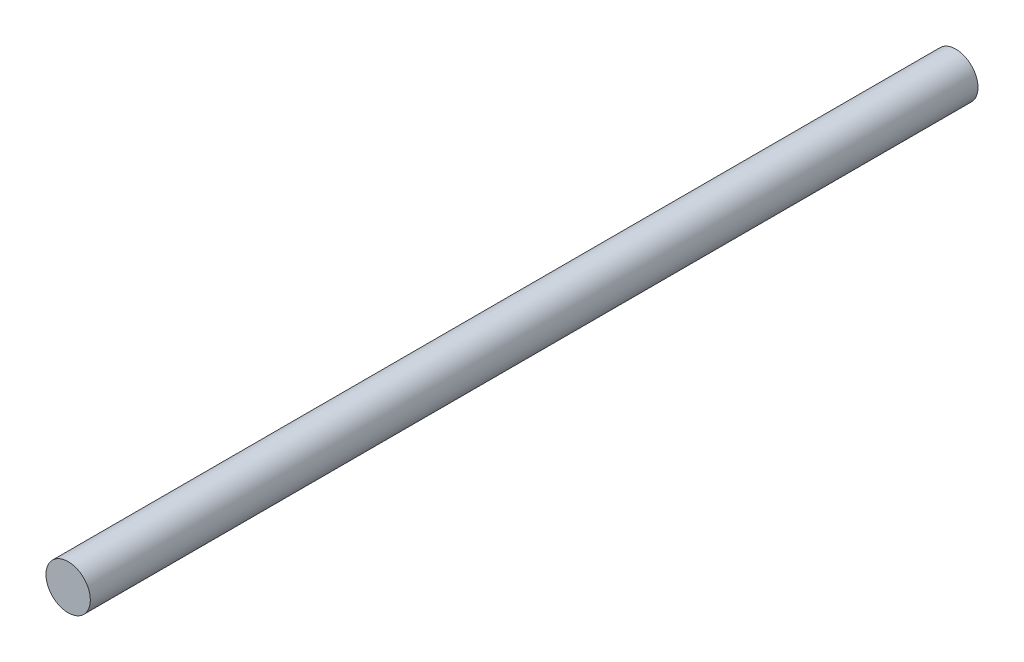
SolidWorks part; units mm, degrees
ref_plane "Front" through (0, 0, 0) normal (0, 0, 1) x (1, 0, 0)
ref_plane "Top" through (0, 0, 0) normal (0, 1, 0) x (1, 0, 0)
ref_plane "Right" through (0, 0, 0) normal (1, 0, 0) x (0, 0, -1)
sketch "Sketch1" plane through (0, 0, 0) normal (0, 0, 1) x (1, 0, 0)
  circle A0 centre (0, 0) radius 7.9375
  dimension "D1" = 15.875
extrude "Extrude1" add sketch "Sketch1" along normal blind 139.7 and the other way blind 177.8
ref_axis "Axis1" through (0, 0, 139.7) along (0, 0, -1)
